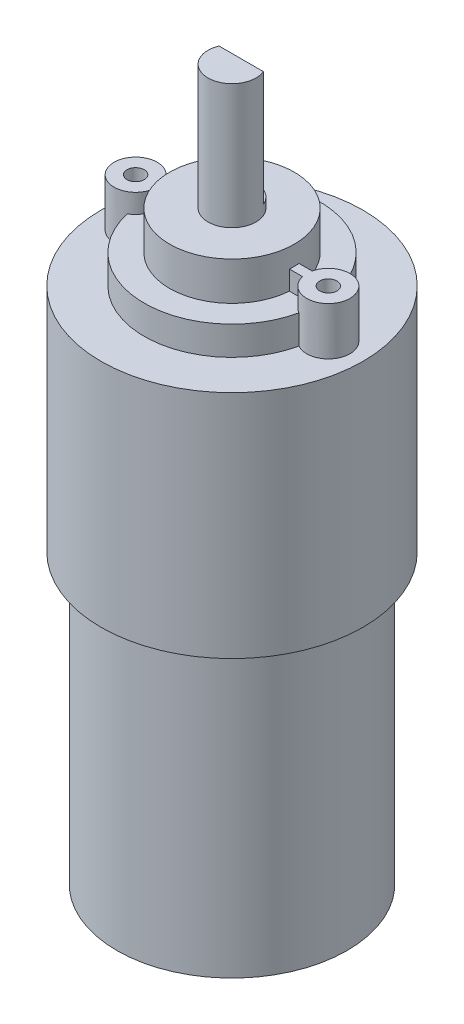
SolidWorks part; units mm, degrees
ref_plane "Alzado" through (0, 0, 0) normal (0, 0, 1) x (1, 0, 0)
ref_plane "Planta" through (0, 0, 0) normal (0, 1, 0) x (1, 0, 0)
ref_plane "Vista lateral" through (0, 0, 0) normal (1, 0, 0) x (0, 0, -1)
sketch "Croquis1" plane through (0, 0, 0) normal (0, 0, 1) x (1, 0, 0)
  line L0 (0, 65.6872) -> (0, -89.1873) construction
  line L1 (0, 30.5) -> (-6.5, 30.5)
  line L2 (-6.5, 30.5) -> (-6.5, 26.5)
  line L3 (-6.5, 26.5) -> (-9.15, 26.5)
  line L4 (-9.15, 26.5) -> (-9.15, 23.5)
  line L5 (-9.15, 23.5) -> (-13.65, 23.5)
  line L6 (-13.65, 23.5) -> (-13.65, -0.5)
  line L7 (-13.65, -0.5) -> (-12, -0.5)
  line L8 (-12, -0.5) -> (-12, -30.5)
  line L9 (-12, -30.5) -> (0, -30.5)
  line L10 (0, -30.5) -> (0, 30.5)
  line L11 (0, 30.5) -> (0, 43.5)
  line L12 (0, 43.5) -> (-2.5, 43.5)
  line L13 (-2.5, 43.5) -> (-2.5, 30.5)
  line L14 (-2.5, 30.5) -> (0, 30.5)
  point P5 (0, 0)
  dimension "D1" = 6.5
  dimension "D2" = 4
  dimension "D3" = 9.15
  dimension "D4" = 13.65
  dimension "D5" = 24
  dimension "D6" = 30
  dimension "D7" = 3
  dimension "D8" = 12
  dimension "D9" = 13
  dimension "D10" = 2.5
revolve "Revolución1" add sketch "Croquis1" angle 360 about L0 region at (-6.2154, -0.52, 0) region at (-1.25, 37, 0)
sketch "Croquis2" plane through (0, 43.5, 0) normal (0, 1, 0) x (1, 0, 0)
  line L0 (-2.3083, 0.96) -> (2.3083, 0.96)
  circle A1 centre (0, 0) radius 2.5
  circle A2 centre (0, 0) radius 2.5
  circle M3 centre (0, 0) radius 2.5
  dimension "D2" = 0.96
  dimension "D1" = 0
extrude "Cortar-Extruir1" cut sketch "Croquis2" against normal blind 12 contours L0 M3 region at (0, 43.5, -1.5959)
sketch "Croquis4" plane through (0, 23.5, 0) normal (0, 1, 0) x (1, 0, 0)
  line L0 (0, 5.4331) -> (0, -4.2682) construction
  line L1 (9, 0.5) -> (-9, 0.5)
  line L2 (0, 0.5) -> (0, -0.5)
  line L3 (9, -0.5) -> (-9, -0.5)
  line L4 (-9, 0.5) -> (-9, -0.5)
  line L5 (-12.29, 7.8034) -> (-12.29, -7.8344) construction
  line L6 (0, 0) -> (-16.243, 0) construction
  line L7 (9, 0.5) -> (9, -0.5)
  circle A0 centre (-10.04, 0) radius 2.25
  circle A1 centre (-10.04, 0) radius 0.9
  circle A2 centre (10.04, 0) radius 0.9
  circle A3 centre (10.04, 0) radius 2.25
  point P10 (0, 0)
  circle M11 centre (0, 0) radius 9.15
  dimension "D1" = 1.8
  dimension "D2" = 4.5
  dimension "D3" = 1
  dimension "D4" = 12.29
  dimension "D5" = 9
extrude "Saliente-Extruir1" add sketch "Croquis4" along normal blind 5 contours A1 A0 M11 | A1 A0 L3 L4 L1 M11 | A0 L3 L2 L1 | L3 A3 L1 L2 | A3 A2 L1 L7 L3 M11 | A3 L3 L7 L1 | A3 A2 M11 | L3 A0 L1 L4 region at (8.4042, 23.5, 0) region at (8.4231, 23.5, -0.5413) region at (3.9043, 23.5, 0) region at (-3.9043, 23.5, 0) region at (11.1478, 23.5, -1.8937) region at (-8.4042, 23.5, 0) region at (-8.4231, 23.5, -0.5413) region at (-9.1453, 23.5, -1.0563)
